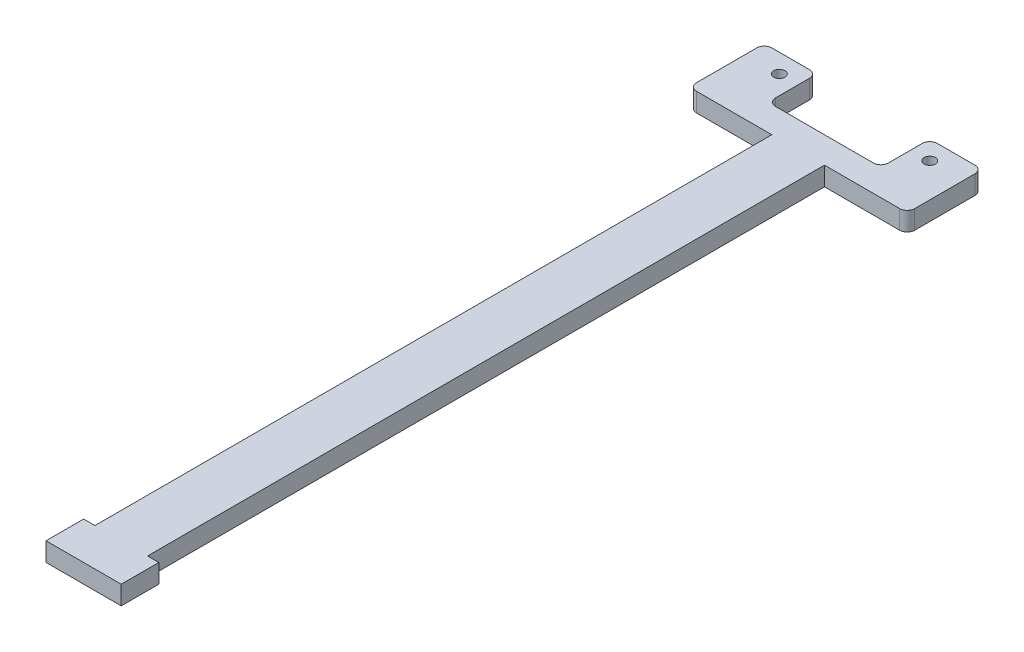
SolidWorks part; units mm, degrees
ref_plane "Front Plane" through (0, 0, 0) normal (0, 0, 1) x (1, 0, 0)
ref_plane "Top Plane" through (0, 0, 0) normal (0, 1, 0) x (1, 0, 0)
ref_plane "Right Plane" through (0, 0, 0) normal (1, 0, 0) x (0, 0, -1)
sketch "Sketch1" plane through (0, 0, 0) normal (0, 1, 0) x (1, 0, 0)
  line L1 (9, -10) -> (9, 0)
  line L2 (9, 0) -> (6, 0)
  line L3 (6, 0) -> (6, 180)
  line L4 (6, 180) -> (28, 180)
  line L5 (28, 180) -> (28, 200)
  line L6 (28, 200) -> (-30, 200)
  line L7 (-30, 200) -> (-30, 180)
  line L8 (-30, 180) -> (-8, 180)
  line L9 (-8, 180) -> (-8, 0)
  line L10 (-8, 0) -> (-11, 0)
  line L11 (-11, 0) -> (-11, -10)
  line L13 (-11, -10) -> (9, -10)
  dimension "D1" = 20
  dimension "D2" = 180
  dimension "D3" = 10
  dimension "D4" = 14
  dimension "D5" = 3
  dimension "D6" = 58
  dimension "D7" = 22
  dimension "D8" = 20
  dimension "D9" = 10
  dimension "D10" = 6
extrude "Boss-Extrude1" add sketch "Sketch1" along normal blind 5
sketch "Sketch2" plane through (0, 5, 0) normal (0, 1, 0) x (1, 0, 0)
  line L0 (28, 180) -> (28, 200) construction
  line L1 (28, 200) -> (-30, 200) construction
  line L2 (-16, 200) -> (-16, 187)
  line L3 (-16, 187) -> (14, 187)
  line L4 (14, 187) -> (14, 200)
  line L5 (14, 200) -> (-16, 200)
  circle A0 centre (-21, 195) radius 1.5
  circle A1 centre (19, 195) radius 1.5
  dimension "D1" = 3
  dimension "D2" = 3
  dimension "D3" = 40
  dimension "D4" = 30
  dimension "D5" = 5
  dimension "D6" = 14
  dimension "D7" = 5
  dimension "D8" = 5
extrude "Cut-Extrude1" cut sketch "Sketch2" against normal blind 10
fillet "Fillet1" radius 2 8 edges at (28, 2.5, -180) (28, 2.5, -200) (-30, 2.5, -180) (-30, 2.5, -200) (14, 2.5, -187) (14, 2.5, -200) (-16, 2.5, -187) (-16, 2.5, -200)
